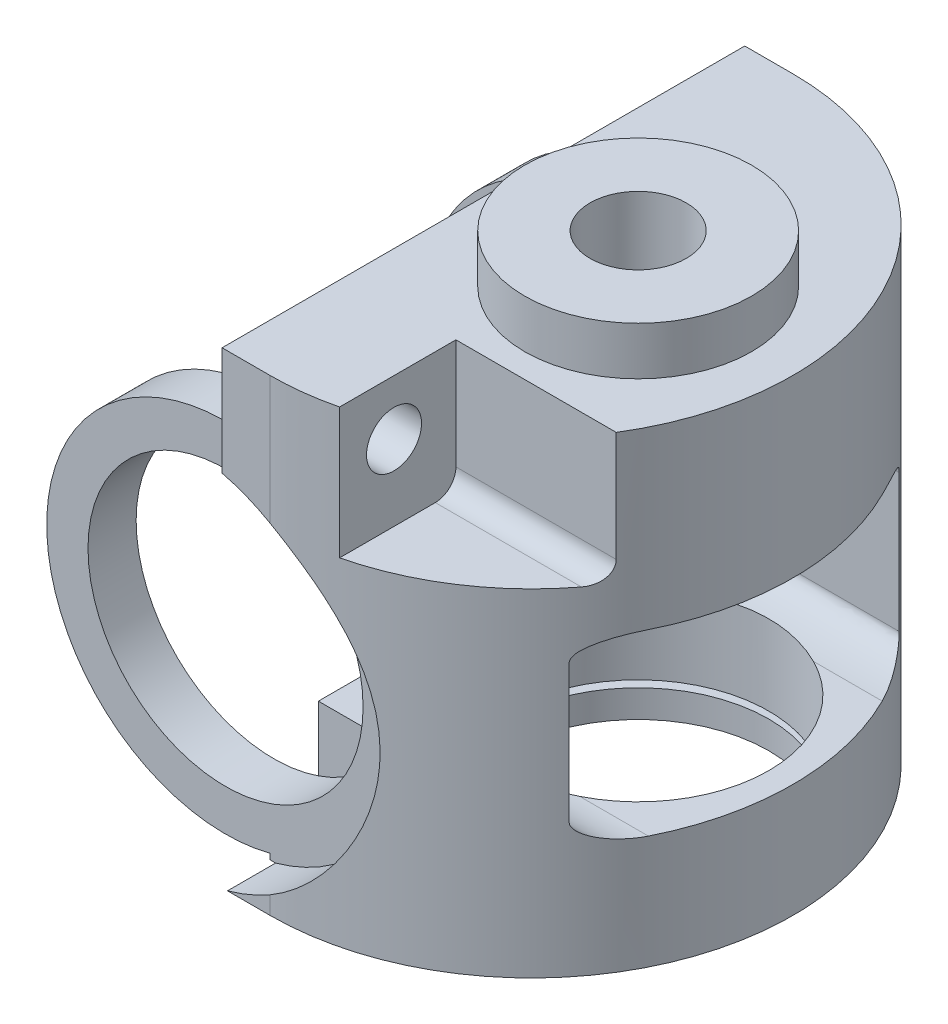
SolidWorks part; units mm, degrees
ref_plane "Plan de face" through (0, 0, 0) normal (0, 0, 1) x (1, 0, 0)
ref_plane "Plan de dessus" through (0, 0, 0) normal (0, 1, 0) x (1, 0, 0)
ref_plane "Plan de droite" through (0, 0, 0) normal (1, 0, 0) x (0, 0, -1)
sketch "Sketch2" plane through (0, 0, 0) normal (0, 1, 0) x (1, 0, 0)
  line L0 (-3.5, -19) -> (-3.5, 19)
  line L1 (-3.5, 19) -> (0, 19)
  line L2 (-3.5, -19) -> (0, -19)
  line L3 (19, 0) -> (19, 16.5672) construction
  arc A0 (0, -19) -> (0, 19) centre (0, 0) ccw
  circle A1 centre (7.75, 0) radius 3.5
  point P7 (-3.5, 0)
  dimension "D1" = 19
  dimension "D3" = 22.5
  dimension "D4" = 11.25
  dimension "D5" = 7
  dimension "D2" = 38
extrude "Boss-Extrude1" add sketch "Sketch2" along normal blind 34
sketch "Sketch19" plane through (0, 34, 0) normal (0, 1, 0) x (1, 0, 0)
  circle A0 centre (7.75, 0) radius 8.25
  circle A1 centre (7.75, 0) radius 3.5
  dimension "D1" = 16.5
  dimension "D2" = 7
extrude "Boss-Extrude3" add sketch "Sketch19" along normal blind 3.5
sketch "Sketch7" plane through (0, 0, 19) normal (0, 0, -1) x (-1, 0, 0)
  line L0 (6.75, 13) -> (0, 0) construction
  circle A3 centre (6.75, 13) radius 13.5
  dimension "D1" = 13
  dimension "D2" = 6.75
  dimension "D3" = 27
extrude "Cut-Extrude4" cut sketch "Sketch7" along normal blind 3.5 contours A3
sketch "Sketch25" plane through (0, 0, 15.5) normal (0, 0, 1) x (1, 0, 0)
  circle A0 centre (-6.75, 13) radius 13
  dimension "D1" = 26
extrude "Boss-Extrude4" add sketch "Sketch25" against normal blind 3.5
sketch "Sketch27" plane through (0, 0, 15.5) normal (0, 0, 1) x (1, 0, 0)
  circle A0 centre (-6.75, 13) radius 10
  dimension "D1" = 20
extrude "Cut-Extrude13" cut sketch "Sketch27" against normal up to surface (3.5 mm away) up to face at (-11.625, 13, 12)
pattern_linear "LPattern3" count 2 spacing 34.5 along (0, 0, -1) of "Cut-Extrude4"
pattern_linear "LPattern4" count 2 spacing 27.5 along (0, 0, -1) of "Boss-Extrude4", "Cut-Extrude13"
sketch "Sketch6" plane through (-3.5, 0, 0) normal (1, 0, 0) x (0, 0, -1)
  line L0 (15.5, 0) -> (-15.5, 0) construction
  line L1 (12, 21.25) -> (-12, 21.25)
  line L2 (12, 21.25) -> (12, 8.25)
  line L3 (12, 8.25) -> (-12, 8.25)
  line L4 (-12, 21.25) -> (-12, 8.25)
  point P1 (0, 8.25)
  dimension "D1" = 8.25
  dimension "D2" = 13
  dimension "D3" = 24
extrude "Cut-Extrude3" cut sketch "Sketch6" along normal through all
fillet "Fillet2" radius 3.5 2 edges at (8.3904, 8.25, -12) (6.8161, 21.25, -12) second distance 1.5 first distance on face at (7.75, 8.25, 3.5) first distance on face at (7.75, 21.25, -3.5)
fillet "Fillet3" radius 3.5 2 edges at (8.3904, 8.25, 12) (6.8161, 21.25, 12) second distance 1.5 first distance on face at (7.75, 8.25, 3.5) first distance on face at (7.75, 21.25, -3.5)
sketch "Sketch16" plane through (-3.5, 0, 0) normal (-1, 0, 0) x (0, 0, 1)
  line L1 (-19, 34) -> (19, 34) construction
  line L2 (-19, 34) -> (-19, 26.103) construction
  point P0 (-11, 31.5)
  dimension "D1" = 8
  dimension "D2" = 2.5
hole_wizard "M2 Tapped Hole1" positions "Sketch16" profile "Sketch15" tap size "M2" standard "ISO"
sketch "Sketch15" plane through (-3.5, 31.5, -11) normal (0, 1, 0) x (0, 0, 1)
  line L0 (0, 0) -> (0, 5.9807)
  line L1 (0, 5.9807) -> (0.8, 5.5)
  line L2 (0.8, 5.5) -> (0.8, 0)
  line L5 (0.8, 0) -> (0, 0)
  line L10 (0, 5.9807) -> (-0.8, 5.5) construction
  line L11 (0, -6.35) -> (0, 107.95) construction
  dimension "Tap Drill Dia." = 1.6
  dimension "Tap Drill Depth" = 5.5
  dimension "Drill Angle" = 118
cosmetic thread "Hole Thread1" parameters "D1"=4.5, "D2"=2
sketch "Sketch17" plane through (-3.5, 0, 0) normal (-1, 0, 0) x (0, 0, 1)
  line L1 (-19, 34) -> (19, 34) construction
  line L2 (19, 34) -> (19, 26.103) construction
  circle A1 centre (14.5, 30) radius 2
  dimension "D1" = 4
  dimension "D2" = 4.5
  dimension "D3" = 4
extrude "Cut-Extrude5" cut sketch "Sketch17" against normal blind 8
sketch "Sketch18" plane through (4.5, 0, 0) normal (-1, 0, 0) x (0, 0, 1)
  line L0 (10, 34) -> (14.5, 30) construction
  line L6 (0, 0) -> (0, 34) construction
  line L7 (-15.5, 0) -> (15.5, 0) construction
  line L8 (10, 26) -> (10, 34)
  line L9 (19, 34) -> (10, 34)
  line L10 (19, 24.5) -> (19, 34)
  line L11 (19, 24.5) -> (11.5, 24.5)
  arc A3 (10, 26) -> (11.5, 24.5) centre (11.5, 26) ccw
  dimension "D1" = 9
  dimension "D2" = 9.5
  dimension "D3" = 1.5
  dimension "D4" = 4
  dimension "D5" = 8
  dimension "D6" = 7.5
  dimension "D7" = 4.5
extrude "Cut-Extrude6" cut sketch "Sketch18" against normal up to next
sketch "Sketch20" plane through (0, 21.25, 0) normal (0, -1, 0) x (1, 0, 0)
  circle A0 centre (7.75, 0) radius 9.75
  dimension "D1" = 19.5
extrude "Cut-Extrude7" cut sketch "Sketch20" against normal blind 6.25
sketch "Sketch21" plane through (0, 27.5, 0) normal (0, -1, 0) x (1, 0, 0)
  circle A0 centre (7.75, 0) radius 8.5
  dimension "D1" = 17
extrude "Cut-Extrude8" cut sketch "Sketch21" against normal blind 0.5
sketch "Sketch22" plane through (0, 8.25, 0) normal (0, 1, 0) x (1, 0, 0)
  circle A0 centre (7.75, 0) radius 9.5
  dimension "D1" = 19
extrude "Cut-Extrude9" cut sketch "Sketch22" against normal blind 5.75 and the other way blind 1
sketch "Sketch23" plane through (0, 2.5, 0) normal (0, 1, 0) x (1, 0, 0)
  circle A0 centre (7.75, 0) radius 10.5
  dimension "D1" = 21
extrude "Cut-Extrude10" cut sketch "Sketch23" against normal blind 0.5
sketch "Sketch24" plane through (0, 2, 0) normal (0, 1, 0) x (1, 0, 0)
  circle A0 centre (7.75, 0) radius 9.5
  dimension "D1" = 19
extrude "Cut-Extrude11" cut sketch "Sketch24" against normal blind 2
